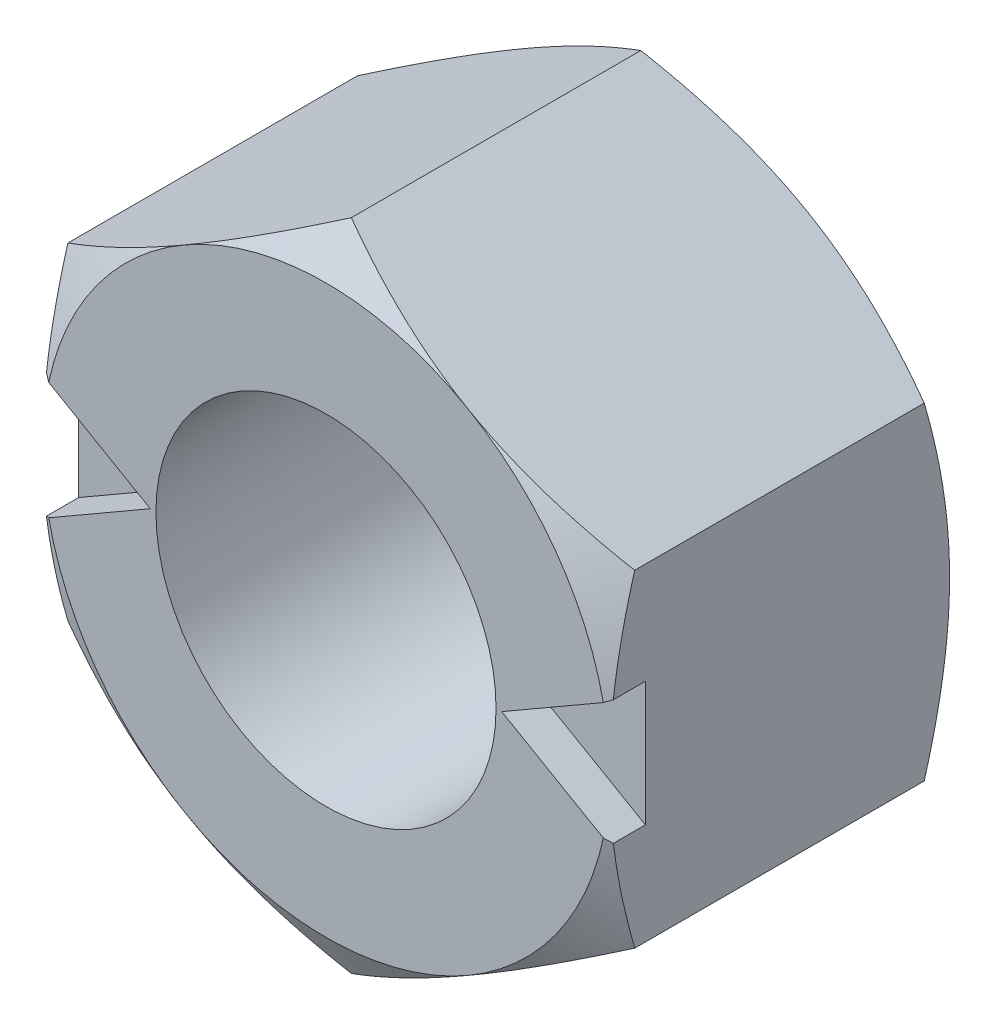
SolidWorks part; units mm, degrees
ref_plane "Front Plane" through (0, 0, 0) normal (0, 0, 1) x (1, 0, 0)
ref_plane "Top Plane" through (0, 0, 0) normal (0, 1, 0) x (1, 0, 0)
ref_plane "Right Plane" through (0, 0, 0) normal (1, 0, 0) x (0, 0, -1)
sketch "Sketch10" plane through (0, 0, 0) normal (1, 0, 0) x (0, 0, -1)
  line L0 (-3, 0) -> (3, 0) construction
  line L1 (-3, -5) -> (-3, 5) construction
  line L2 (-3, -3) -> (-3, 3) construction
  line L3 (-3.9375, 3.1083) -> (-2.9375, 3.1083) construction
  line L4 (-2.9375, 3.1083) -> (-3.4375, 2.2422) construction
  line L5 (-3.4375, 2.2422) -> (-3.9375, 3.1083) construction
  line L6 (-3.4375, 3.1083) -> (-3.4375, 3) construction
  line L7 (-3.4375, 2.2422) -> (-3.4375, 2.3505) construction
  line L8 (-3.875, 3) -> (-3, 3) construction
  line L9 (-3.9062, 3.0541) -> (-2.9687, 3.0541) construction
  line L10 (-3.5, 2.3505) -> (-3.375, 2.3505) construction
  line L11 (3, -5) -> (3, 5) construction
  point P4 (0, 0)
  point P8 (-3, 0)
  point P11 (-3, 0)
  point P20 (-3.4375, 3)
  point P23 (-3.4375, 3.0541)
  point P26 (-3.4375, 2.3505)
  point P27 (-2.365, 0)
  point P28 (3, 0)
  dimension "Height" = 6
  dimension "Width" = 10
  dimension "Thread Size" = 6
  dimension "Thread Pitch" = 1
  dimension "D1" = 0.125
  dimension "D2" = 0.635
sketch "Sketch11" plane through (0, 0, 0) normal (0, 0, 1) x (1, 0, 0)
  line L0 (0, -5) -> (0, 5) construction
  line L1 (-5, 0) -> (-3.1, 0) construction
  line L2 (-3.1, 0) -> (-5, 1.097) construction
  line L3 (-5, 1.097) -> (-5, 0) construction
  line L4 (0, 0) -> (2.1213, -2.1213) construction
  circle A0 centre (0, 0) radius 3 construction
  circle A1 centre (0, 0) radius 5 construction
  point P10 (-3, 0)
  point P14 (2.1213, -2.1213)
  dimension "D1" = 0.1
  dimension "D2" = 30
  dimension "D3" = 135
sketch "Sketch1" plane through (0, 0, 0) normal (0, 0, 1) x (1, 0, 0)
  line L1 (0, 5.7735) -> (-5, 2.8868)
  line L2 (-5, 2.8868) -> (-5, -2.8868)
  line L3 (-5, -2.8868) -> (0, -5.7735)
  line L4 (0, -5.7735) -> (5, -2.8868)
  line L5 (5, -2.8868) -> (5, 2.8868)
  line L6 (5, 2.8868) -> (0, 5.7735)
  circle A0 centre (0, 0) radius 5 construction
  circle A1 centre (0, 0) radius 5 construction
extrude "Extrude1" add sketch "Sketch1" along normal up to vertex (3 mm away) and the other way up to vertex (3 mm away) up to point (0, 0, 3) other way up to point (0, 0, -3)
sketch "Sketch2" plane through (0, 0, 3) normal (0, 0, -1) x (-1, 0, 0)
  circle A1 centre (0, 0) radius 5
  circle A2 centre (0, 0) radius 5 construction
extrude "Cut-Extrude1" cut sketch "Sketch2" along normal through all draft 60 flip side to cut
sketch "Sketch3" plane through (0, 0, -3) normal (0, 0, 1) x (1, 0, 0)
  circle A0 centre (0, 0) radius 5 construction
  circle A2 centre (0, 0) radius 5
extrude "Cut-Extrude2" cut sketch "Sketch3" along normal through all draft 60 flip side to cut
sketch "Sketch4" plane through (0, 0, -3) normal (0, 0, -1) x (-1, 0, 0)
  circle A0 centre (0, 0) radius 3
  circle A1 centre (0, 0) radius 3 construction
extrude "Cut-Extrude3" cut sketch "Sketch4" against normal through all
sketch "Sketch12" plane through (0, 0, 3) normal (0, 0, 1) x (1, 0, 0)
  line L0 (-3.1, 0) -> (-5, 1.097) construction
  line L1 (-3.1, 0) -> (-5, 1.097)
  line L2 (-5, 0) -> (-3.1, 0) construction
  line L3 (-5, 0) -> (-3.1, 0) construction
  line L4 (0, -3) -> (0, 3) construction
  line L5 (0, -3) -> (0, 3) construction
  line L6 (-3.1, 0) -> (-5, -1.097)
  line L7 (3.1, 0) -> (5, -1.097)
  line L8 (3.1, 0) -> (5, 1.097)
  line L9 (-5, 1.097) -> (-5, -1.097)
  line L10 (5, 1.097) -> (5, -1.097)
extrude "Cut-Extrude7" cut sketch "Sketch12" against normal up to vertex (0.635 mm away) up to point (0, 0, 2.365)
sketch "Sketch5" [suppressed] plane through (0, 0, 3) normal (0, 0, -1) x (-1, 0, 0)
  circle A1 centre (0, 0) radius 3
  point P0 (0, 3)
curve "Helix/Spiral1" [suppressed] pitch 1 height 7 turns 7 parameters "pitch"=1
sketch "Sketch6" [suppressed] plane through (0, 0, 0) normal (1, 0, 0) x (0, 0, -1)
  line L0 (-3.9062, 3.0541) -> (-2.9687, 3.0541)
  line L1 (-2.9687, 3.0541) -> (-3.375, 2.3505)
  line L2 (-3.375, 2.3505) -> (-3.5, 2.3505)
  line L3 (-3.5, 2.3505) -> (-3.9062, 3.0541)
sweep "Sweep1" [suppressed] add profiles "Sketch6" path "Helix/Spiral1"
sketch "Sketch7" [suppressed] plane through (0, 0, -3) normal (0, 0, -1) x (-1, 0, 0)
  circle A0 centre (0, 0) radius 3.1083
  point P2 (0, 3.1083)
extrude "Cut-Extrude4" [suppressed] cut sketch "Sketch7" against normal through all draft 45 and the other way through all
sketch "Sketch8" [suppressed] plane through (0, 0, 3) normal (0, 0, 1) x (1, 0, 0)
  line L0 (0, 0) -> (-2.6918, 1.5541) construction
  circle A1 centre (0, 0) radius 3.1083
  circle A2 centre (0, 0) radius 3.1083
  dimension "D1" = 0
extrude "Cut-Extrude5" [suppressed] cut sketch "Sketch8" against normal through all draft 45 and the other way through all
equation "\"D3@Helix/Spiral1\" = \"Thread Pitch@Sketch10\" + \"Height@Sketch10\""
equation "\"D1@Sketch10\" = \"Thread Pitch@Sketch10\" / 8"
equation "\"pitch@Helix/Spiral1\" = \"Thread Pitch@Sketch10\""
